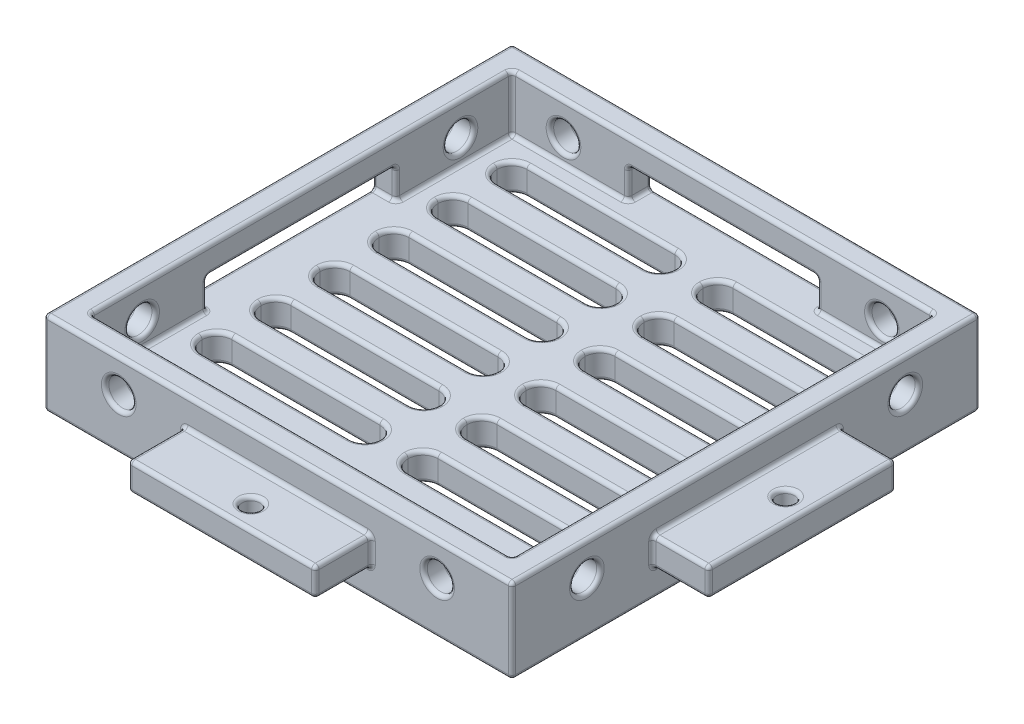
SolidWorks part; units mm, degrees
ref_plane "Front Plane" through (0, 0, 0) normal (0, 0, 1) x (1, 0, 0)
ref_plane "Top Plane" through (0, 0, 0) normal (0, 1, 0) x (1, 0, 0)
ref_plane "Right Plane" through (0, 0, 0) normal (1, 0, 0) x (0, 0, -1)
sketch "Sketch1" plane through (0, 0, 0) normal (0, 1, 0) x (1, 0, 0)
  line L1 (0, 0) -> (50, 0)
  line L2 (0, 0) -> (0, -50)
  line L3 (0, -50) -> (50, -50)
  line L4 (50, 0) -> (50, -50)
  dimension "D1" = 50
  dimension "D2" = 50
extrude "Boss-Extrude1" add sketch "Sketch1" along normal blind 3
sketch "Sketch2" plane through (0, 3, 0) normal (0, 1, 0) x (1, 0, 0)
  line L4 (2.5, -2.5) -> (2.5, -47.5)
  line L5 (2.5, -47.5) -> (47.5, -47.5)
  line L6 (47.5, -47.5) -> (47.5, -2.5)
  line L7 (47.5, -2.5) -> (2.5, -2.5)
  line L8 (0, 0) -> (0, -50)
  line L9 (0, -50) -> (50, -50)
  line L10 (50, -50) -> (50, 0)
  line L11 (50, 0) -> (0, 0)
  line L12 (0, 0) -> (0, -50)
  line L13 (0, -50) -> (50, -50)
  line L14 (50, -50) -> (50, 0)
  line L15 (50, 0) -> (0, 0)
  dimension "D1" = 0
  dimension "D2" = 2.5
extrude "Boss-Extrude2" add sketch "Sketch2" along normal blind 6
sketch "Sketch3" plane through (2.5, 0, 0) normal (1, 0, 0) x (0, 0, -1)
  line L0 (-2.5, 3) -> (-47.5, 3) construction
  line L1 (-35.1, 3) -> (-14.9, 3)
  line L2 (-35.1, 3) -> (-35.1, 6.2)
  line L3 (-35.1, 6.2) -> (-14.9, 6.2)
  line L4 (-14.9, 3) -> (-14.9, 6.2)
  line L5 (-2.5, 9) -> (-47.5, 9) construction
  point P8 (-25, 9)
  dimension "D1" = 3.2
  dimension "D2" = 20.2
  dimension "D3" = 10.1
extrude "Cut-Extrude1" cut sketch "Sketch3" against normal blind 5
sketch "Sketch4" plane through (50, 0, 0) normal (1, 0, 0) x (0, 0, -1)
  line L0 (-50, 0) -> (0, 0) construction
  line L1 (-35, 6) -> (-15, 6)
  line L2 (-35, 6) -> (-35, 3)
  line L3 (-35, 3) -> (-15, 3)
  line L4 (-15, 6) -> (-15, 3)
  line L5 (-50, 9) -> (0, 9) construction
  point P8 (-25, 9)
  dimension "D1" = 3
  dimension "D2" = 3
  dimension "D3" = 20
  dimension "D4" = 10
extrude "Boss-Extrude3" add sketch "Sketch4" along normal blind 6
sketch "Sketch5" plane through (0, 0, 0) normal (-1, 0, 0) x (0, 0, 1)
  line L0 (0, 9) -> (0, 0) construction
  line L1 (50, 9) -> (50, 0) construction
  line L2 (0, 9) -> (50, 9) construction
  circle A0 centre (8, 5.5) radius 1.45
  circle A1 centre (42, 5.5) radius 1.45
  dimension "D1" = 2.9
  dimension "D2" = 2.9
  dimension "D4" = 8
  dimension "D6" = 3.5
  dimension "D3" = 8
  dimension "D5" = 3.5
extrude "Cut-Extrude2" cut sketch "Sketch5" against normal through all
sketch "Sketch9" plane through (0, 6, 0) normal (0, 1, 0) x (1, 0, 0)
  line L0 (50, -50) -> (50, 0) construction
  circle A0 centre (53.55, -24.3336) radius 0.95
  point P4 (0, 0)
  dimension "D1" = 1.9
  dimension "D2" = 3.55
extrude "Cut-Extrude3" cut sketch "Sketch9" against normal through all
ref_plane "Plane1" through (0, 0, 25) normal (0, 0, 1) x (1, 0, 0)
sketch "Sketch8" plane through (0, 0, 25) normal (0, 0, 1) x (1, 0, 0)
  line L0 (25, 7.0903) -> (25, 0.7945) construction
  line L2 (50, 9) -> (50, 0) construction
  dimension "D1" = 25
pattern_circular "CirPattern1" count 2 every 90 about axis through (25, 0, 25) along (0, 1, 0) of "Cut-Extrude1", "Boss-Extrude3", "Cut-Extrude2", "Cut-Extrude3"
sketch "Sketch10" plane through (0, 3, 0) normal (0, 1, 0) x (1, 0, 0)
  line L0 (2.5, -2.5) -> (2.5, -14.9) construction
  line L1 (4.5, -4.5) -> (23.5, -4.5)
  line L2 (4.5, -4.5) -> (4.5, -7.7)
  line L3 (4.5, -7.7) -> (23.5, -7.7)
  line L4 (23.5, -4.5) -> (23.5, -7.7)
  line L5 (14.9, -2.5) -> (2.5, -2.5) construction
  line L6 (26.5, -4.5) -> (26.5, -7.7)
  line L7 (26.5, -4.5) -> (45.5, -4.5)
  line L8 (45.5, -4.5) -> (45.5, -7.7)
  line L9 (26.5, -7.7) -> (45.5, -7.7)
  line L10 (26.5, -10.8) -> (26.5, -14)
  line L11 (26.5, -10.8) -> (45.5, -10.8)
  line L12 (45.5, -10.8) -> (45.5, -14)
  line L13 (26.5, -14) -> (45.5, -14)
  line L14 (26.5, -17.1) -> (26.5, -20.3)
  line L15 (26.5, -17.1) -> (45.5, -17.1)
  line L16 (45.5, -17.1) -> (45.5, -20.3)
  line L17 (26.5, -20.3) -> (45.5, -20.3)
  line L18 (26.5, -23.4) -> (26.5, -26.6)
  line L19 (26.5, -23.4) -> (45.5, -23.4)
  line L20 (45.5, -23.4) -> (45.5, -26.6)
  line L21 (26.5, -26.6) -> (45.5, -26.6)
  line L22 (26.5, -29.7) -> (26.5, -32.9)
  line L23 (26.5, -29.7) -> (45.5, -29.7)
  line L24 (45.5, -29.7) -> (45.5, -32.9)
  line L25 (26.5, -32.9) -> (45.5, -32.9)
  line L26 (26.5, -36) -> (26.5, -39.2)
  line L27 (26.5, -36) -> (45.5, -36)
  line L28 (45.5, -36) -> (45.5, -39.2)
  line L29 (26.5, -39.2) -> (45.5, -39.2)
  line L30 (26.5, -42.3) -> (26.5, -45.5)
  line L31 (26.5, -42.3) -> (45.5, -42.3)
  line L32 (45.5, -42.3) -> (45.5, -45.5)
  line L33 (26.5, -45.5) -> (45.5, -45.5)
  line L34 (4.5, -10.8) -> (4.5, -14)
  line L35 (4.5, -10.8) -> (23.5, -10.8)
  line L36 (23.5, -10.8) -> (23.5, -14)
  line L37 (4.5, -14) -> (23.5, -14)
  line L38 (4.5, -17.1) -> (4.5, -20.3)
  line L39 (4.5, -17.1) -> (23.5, -17.1)
  line L40 (23.5, -17.1) -> (23.5, -20.3)
  line L41 (4.5, -20.3) -> (23.5, -20.3)
  line L42 (4.5, -23.4) -> (4.5, -26.6)
  line L43 (4.5, -23.4) -> (23.5, -23.4)
  line L44 (23.5, -23.4) -> (23.5, -26.6)
  line L45 (4.5, -26.6) -> (23.5, -26.6)
  line L46 (4.5, -29.7) -> (4.5, -32.9)
  line L47 (4.5, -29.7) -> (23.5, -29.7)
  line L48 (23.5, -29.7) -> (23.5, -32.9)
  line L49 (4.5, -32.9) -> (23.5, -32.9)
  line L50 (4.5, -36) -> (4.5, -39.2)
  line L51 (4.5, -36) -> (23.5, -36)
  line L52 (23.5, -36) -> (23.5, -39.2)
  line L53 (4.5, -39.2) -> (23.5, -39.2)
  line L54 (4.5, -42.3) -> (4.5, -45.5)
  line L55 (4.5, -42.3) -> (23.5, -42.3)
  line L56 (23.5, -42.3) -> (23.5, -45.5)
  line L57 (4.5, -45.5) -> (23.5, -45.5)
  dimension "D1" = 3.2
  dimension "D2" = 19
  dimension "D3" = 2
  dimension "D4" = 2
  dimension "D5" = 2
  dimension "D6" = 7
extrude "Cut-Extrude4" cut sketch "Sketch10" against normal through all
fillet "Fillet1" radius 1.6 56 edges at (23.5, 1.5, 7.7) (4.5, 1.5, 7.7) (23.5, 1.5, 45.5) (4.5, 1.5, 45.5) (4.5, 1.5, 42.3) (23.5, 1.5, 42.3) (23.5, 1.5, 39.2) (4.5, 1.5, 39.2) (4.5, 1.5, 36) (23.5, 1.5, 36) (23.5, 1.5, 32.9) (4.5, 1.5, 32.9) (4.5, 1.5, 29.7) (23.5, 1.5, 29.7) (23.5, 1.5, 26.6) (4.5, 1.5, 26.6) (4.5, 1.5, 23.4) (23.5, 1.5, 23.4) (23.5, 1.5, 20.3) (4.5, 1.5, 20.3) (4.5, 1.5, 17.1) (23.5, 1.5, 17.1) (45.5, 1.5, 7.7) (26.5, 1.5, 7.7) (26.5, 1.5, 4.5) (45.5, 1.5, 4.5) (45.5, 1.5, 14) (26.5, 1.5, 14) (26.5, 1.5, 10.8) (45.5, 1.5, 10.8) (45.5, 1.5, 20.3) (26.5, 1.5, 20.3) (26.5, 1.5, 17.1) (45.5, 1.5, 17.1) (45.5, 1.5, 26.6) (26.5, 1.5, 26.6) (26.5, 1.5, 23.4) (45.5, 1.5, 23.4) (23.5, 1.5, 14) (4.5, 1.5, 14) (4.5, 1.5, 10.8) (23.5, 1.5, 10.8) (45.5, 1.5, 45.5) (26.5, 1.5, 45.5) (26.5, 1.5, 42.3) (45.5, 1.5, 42.3) (45.5, 1.5, 39.2) (26.5, 1.5, 39.2) (26.5, 1.5, 36) (45.5, 1.5, 36) (45.5, 1.5, 32.9) (26.5, 1.5, 32.9) (26.5, 1.5, 29.7) (45.5, 1.5, 29.7) (23.5, 1.5, 4.5) (4.5, 1.5, 4.5)
fillet "Fillet2" radius 0.4 70 edges at (14, 3, 42.3) (14, 3, 45.5) (14, 0, 42.3) (14, 3, 39.2) (14, 0, 39.2) (14, 0, 17.1) (14, 0, 20.3) (14, 3, 10.8) (36, 3, 42.3) (36, 3, 45.5) (36, 3, 36) (36, 0, 36) (36, 3, 29.7) (36, 3, 23.4) (36, 3, 26.6) (36, 3, 10.8) (36, 3, 14) (14, 3, 4.5) (14, 0, 4.5) (24.7164, 6, 53.55) (25.6664, 3, 54.5) (6.55, 5.5, 50) (40.55, 5.5, 50) (35, 4.5, 56) (25, 6, 56) (35, 3, 53) (25, 3, 0) (35.1, 4.6, 0) (25, 6.2, 0) (47.5, 5.5, 43.45) (50, 5.5, 9.45) (50, 6, 25) (53, 6, 35) (53, 3, 15) (2.5, 4.6, 35.1) (1.25, 6.2, 35.1) (47.5, 9, 25) (2.5, 6, 2.5) (0, 9, 25) (25, 0, 50) (0, 4.5, 50) (23.0314, 0, 7.2314) (23.0314, 0, 45.0314) (4.9686, 0, 42.7686) (23.0314, 3, 38.7314) (23.0314, 3, 32.4314) (4.9686, 0, 30.1686) (23.0314, 3, 30.1686) (23.0314, 0, 23.8686) (4.9686, 3, 19.8314) (4.9686, 0, 19.8314) (23.0314, 3, 17.5686) (23.0314, 0, 17.5686) (45.0314, 0, 7.2314) (26.9686, 0, 13.5314) (26.9686, 3, 11.2686) (45.0314, 0, 11.2686) (45.0314, 3, 19.8314) (26.9686, 3, 17.5686) (45.0314, 3, 26.1314) (4.9686, 0, 11.2686) (26.9686, 0, 45.0314) (45.0314, 0, 42.7686) (26.9686, 0, 38.7314) (26.9686, 3, 36.4686) (45.0314, 3, 36.4686) (26.9686, 3, 32.4314) (23.0314, 3, 4.9686) (4.9686, 3, 4.9686) (4.9686, 0, 4.9686)
equation "\"D2@Sketch9\"=2.6+1.9/2"
equation "\"D2@Sketch10\"=(50-9)/2 - 1.5"
